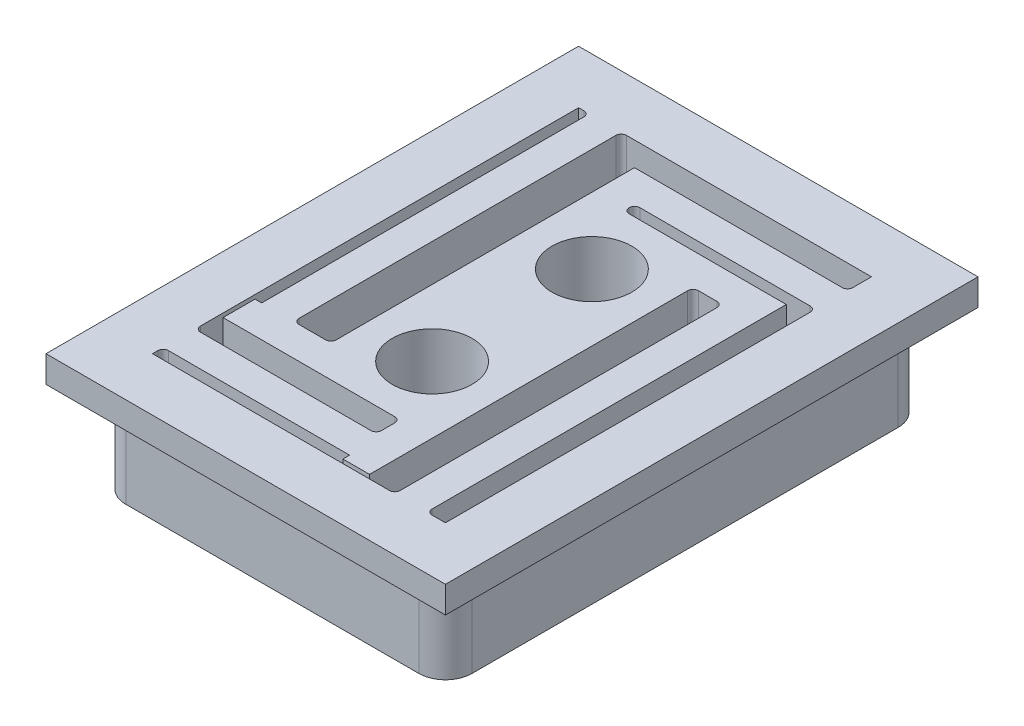
SolidWorks part; units mm, degrees
ref_plane "Front Plane" through (0, 0, 0) normal (0, 0, 1) x (1, 0, 0)
ref_plane "Top Plane" through (0, 0, 0) normal (0, 1, 0) x (1, 0, 0)
ref_plane "Right Plane" through (0, 0, 0) normal (1, 0, 0) x (0, 0, -1)
sketch "Sketch1" plane through (0, 0, 0) normal (0, 1, 0) x (1, 0, 0)
  line L1 (-6.5, -9) -> (6.5, -9)
  line L2 (-6.5, -9) -> (-6.5, 9)
  line L3 (-6.5, 9) -> (6.5, 9)
  line L4 (6.5, -9) -> (6.5, 9)
  line L5 (-6.5, -9) -> (6.5, 9) construction
  line L6 (-6.5, 9) -> (6.5, -9) construction
  point P0 (0, 0)
  dimension "D1" = 18
  dimension "D2" = 13
extrude "Boss-Extrude1" add sketch "Sketch1" along normal blind 3.4
sketch "Sketch2" plane through (0, 3.4, 0) normal (0, 1, 0) x (1, 0, 0)
  line L8 (7.5, -10) -> (7.5, 10)
  line L9 (7.5, 10) -> (-7.5, 10)
  line L10 (-7.5, 10) -> (-7.5, -10)
  line L11 (-7.5, -10) -> (7.5, -10)
  line L12 (7.5, -10) -> (7.5, 10)
  line L13 (7.5, 10) -> (-7.5, 10)
  line L14 (-7.5, 10) -> (-7.5, -10)
  line L15 (-7.5, -10) -> (7.5, -10)
  dimension "D1" = 1
extrude "Boss-Extrude2" add sketch "Sketch2" along normal blind 1
sketch "Sketch3" plane through (0, 0, 0) normal (0, -1, 0) x (1, 0, 0)
  line L0 (0, -3) -> (0, 3)
  line L1 (1.9, 5.5) -> (1.9, 7) construction
  line L2 (1.3, 5.5) -> (1.3, 6.4) construction
  line L3 (-1.9, -5.5) -> (-1.9, -6.5) construction
  line L4 (-1.3, -5.5) -> (-1.3, -5.9) construction
  line L5 (-4.5, -8) -> (-4.5, 4.9) construction
  line L6 (2.5, -5.5) -> (-2.5, -5.5)
  line L7 (2.5, -5.5) -> (2.5, 5.5)
  line L8 (2.5, 5.5) -> (-2.5, 5.5)
  line L9 (5.5, -8) -> (5.5, 8)
  line L10 (5.5, 8) -> (-5.5, 8)
  line L11 (-5.5, 8) -> (-5.5, -8)
  line L12 (-5.5, -8) -> (5.5, -8)
  line L13 (5.5, -8) -> (5.5, 8)
  line L14 (5.5, 8) -> (-5.5, 8)
  line L15 (-5.5, 8) -> (-5.5, -8)
  line L16 (-5.5, -8) -> (5.5, -8)
  line L17 (-2.5, -5.5) -> (-2.5, 5.5)
  line L18 (2.5, -5.5) -> (-2.5, 5.5) construction
  line L19 (2.5, 5.5) -> (-2.5, -5.5) construction
  line L20 (-4.5, 4.9) -> (-2.5, 4.9) construction
  line L21 (4.2, 8) -> (4.2, -4.9) construction
  line L22 (4.2, -4.9) -> (2.5, -4.9) construction
  line L23 (1.9, 5.5) -> (1.9, 7) construction
  line L24 (1.9, 7) -> (-5.5, 7) construction
  line L25 (-1.9, -5.5) -> (-1.9, -6.5) construction
  line L26 (-1.9, -6.5) -> (5.5, -6.5) construction
  line L27 (-3.9, -8) -> (-3.9, 4.3)
  line L28 (-3.9, 4.3) -> (-2.5, 4.3)
  line L29 (-2.5, -5.5) -> (-2.5, -7.1)
  line L30 (-2.5, -7.1) -> (5.5, -7.1)
  line L31 (3.6, 8) -> (3.6, -4.3)
  line L32 (3.6, -4.3) -> (2.5, -4.3)
  line L33 (2.5, 5.5) -> (2.5, 7.6)
  line L34 (2.5, 7.6) -> (-5.5, 7.6)
  line L35 (-5.1, -8) -> (-5.1, 5.5)
  line L36 (-5.1, 5.5) -> (-2.5, 5.5)
  line L37 (-1.3, -5.5) -> (-1.3, -5.9)
  line L38 (-1.3, -5.9) -> (5.5, -5.9)
  line L39 (4.8, 8) -> (4.8, -5.5)
  line L40 (4.8, -5.5) -> (2.5, -5.5)
  line L41 (1.3, 5.5) -> (1.3, 6.4)
  line L42 (1.3, 6.4) -> (-5.5, 6.4)
  line L43 (-5.1, 5.5) -> (-5.35, 5.5)
  line L44 (-5.35, 5.5) -> (-5.35, 4.3)
  line L45 (-5.35, 4.3) -> (-5.1, 4.3)
  line L46 (2.5, 7.6) -> (2.5, 7.85)
  line L47 (2.5, 7.85) -> (1.5, 7.85)
  line L48 (1.5, 7.85) -> (1.5, 7.6)
  line L49 (-4.5, 4.9) -> (-2.5, 4.9) construction
  line L50 (-3.9, 4.3) -> (-2.5, 4.3) construction
  line L51 (4.2, -4.9) -> (2.5, -4.9) construction
  line L52 (3.6, -4.3) -> (2.5, -4.3) construction
  circle A0 centre (0, 3) radius 1.5
  circle A1 centre (0, -3) radius 1.5
  point P4 (0, 0)
  point P7 (0, 0)
  dimension "D2" = 3
  dimension "D1" = 6
  dimension "D4" = 11
  dimension "D5" = 5
  dimension "D6" = 1
  dimension "D7" = 1.3
  dimension "D8" = 1
  dimension "D9" = 1.5
  dimension "D12" = 0.25
  dimension "D13" = 1
  dimension "D14" = 0.25
  dimension "D15" = 0.6
  dimension "D16" = 0.6
  dimension "D17" = 0.6
  dimension "D18" = 0.6
  dimension "D3" = 1
  dimension "D10" = 0.6
  dimension "D11" = 0.6
extrude "Cut-Extrude1" cut sketch "Sketch3" against normal through all contours L30 L29 L17 L28 L27 L16 L13 | L39 L40 L7 L6 L37 L38 L13 L14 | L48 L47 L46 L33 L7 L32 L31 L14 L15 L34 | L45 L44 L43 L36 L8 L41 L42 L15 L16 L35 | A0 | A1 region at (3.65, 0, -5.6547) region at (2.653, 0, 0.6) region at (-2.6548, 0, -6.3) region at (-0.6, 0, 5.6592)
fillet "Fillet1" radius 0.2 16 edges at (-5.1, 2.2, -8) (-3.9, 2.2, -8) (-5.5, 2.2, 6.4) (-5.5, 2.2, 7.6) (4.8, 2.2, 8) (3.6, 2.2, 8) (-3.9, 2.2, 4.3) (-2.5, 2.2, 4.3) (1.3, 2.2, 5.5) (1.3, 2.2, 6.4) (5.5, 2.2, -7.1) (5.5, 2.2, -5.9) (-1.3, 2.2, -5.9) (-1.3, 2.2, -5.5) (3.6, 2.2, -4.3) (2.5, 2.2, -4.3)
fillet "Fillet2" radius 1 4 edges at (-6.5, 1.7, 9) (-6.5, 1.7, -9) (6.5, 1.7, -9) (6.5, 1.7, 9)
mirror "Mirror1" [suppressed] of bodies 103
delete or keep bodies "Body-Delete/Keep 1" [suppressed] type keep bodies bodies 104
